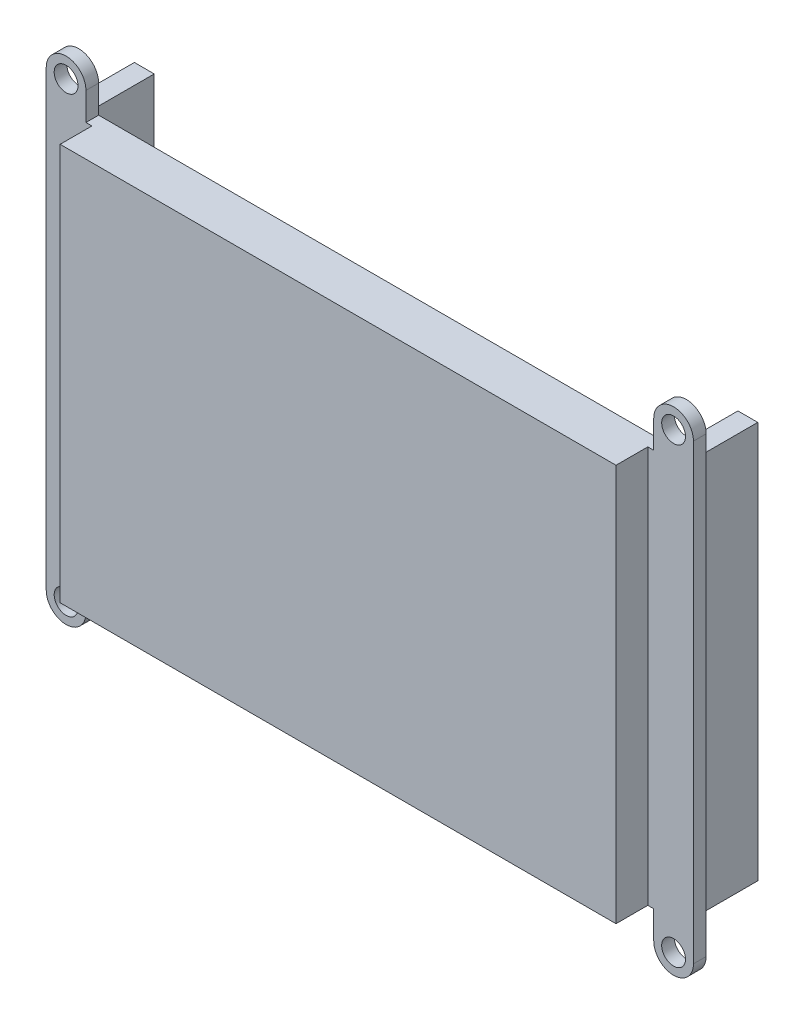
SolidWorks part; units mm, degrees
ref_plane "Vehicle Ground Plane" through (0, 0, 0) normal (0, 0, 1) x (1, 0, 0)
ref_plane "Vehicle Centreline Plane" through (0, 0, 0) normal (0, 1, 0) x (1, 0, 0)
ref_plane "Roll Hoop Plane" through (0, 0, 0) normal (1, 0, 0) x (0, 0, -1)
ref_axis "X-Axis" through (-88.99, 0, 0) along (1, 0, 0)
ref_axis "Y-Axis" through (0, 55, 0) along (0, -1, 0)
ref_axis "Z-Axis" through (0, 0, -88.99) along (0, 0, 1)
sketch "Sketch1" plane through (0, 0, 0) normal (0, 0, 1) x (1, 0, 0)
  line L1 (-35, -25) -> (35, -25)
  line L2 (-35, -25) -> (-35, 25)
  line L3 (-35, 25) -> (35, 25)
  line L4 (35, -25) -> (35, 25)
  line L5 (-35, -25) -> (35, 25) construction
  line L6 (-35, 25) -> (35, -25) construction
  point P0 (0, 0)
  dimension "D1" = 70
  dimension "D2" = 50
extrude "Boss-Extrude1" add sketch "Sketch1" along normal blind 4
sketch "Sketch2" plane through (0, 0, 0) normal (0, 0, -1) x (-1, 0, 0)
  line L1 (-40.75, -25) -> (40.75, -25)
  line L2 (-40.75, -25) -> (-40.75, 25)
  line L3 (-40.75, 25) -> (40.75, 25)
  line L4 (40.75, -25) -> (40.75, 25)
  line L5 (-40.75, -25) -> (40.75, 25) construction
  line L6 (-40.75, 25) -> (40.75, -25) construction
  point P0 (0, 0)
  dimension "D1" = 50
  dimension "D2" = 81.5
extrude "Boss-Extrude2" add sketch "Sketch2" along normal blind 1.6
sketch "Sketch4" plane through (0, 0, 0) normal (0, 0, 1) x (1, 0, 0)
  line L0 (-40.75, 25) -> (-35, 25) construction
  line L1 (-40.75, -25) -> (-40.75, 25) construction
  line L2 (-40.75, 28.5) -> (-40.75, 25)
  line L3 (-40.75, 25) -> (-35.75, 25)
  line L4 (-35.75, 25) -> (-35.75, 28.5)
  line L5 (-40.75, 25) -> (40.75, 25) construction
  line L6 (7.48, 0) -> (-7.48, 0) construction
  line L7 (-35.75, -25) -> (-35.75, -28.5)
  line L8 (-40.75, -25) -> (-35.75, -25)
  line L9 (-40.75, -28.5) -> (-40.75, -25)
  line L10 (0, -7.48) -> (0, 7.48) construction
  line L11 (40.75, -28.5) -> (40.75, -25)
  line L12 (40.75, -25) -> (35.75, -25)
  line L13 (35.75, -25) -> (35.75, -28.5)
  line L14 (35.75, 25) -> (35.75, 28.5)
  line L15 (40.75, 25) -> (35.75, 25)
  line L16 (40.75, 28.5) -> (40.75, 25)
  circle A1 centre (-38.25, 28.5) radius 1.5
  arc A2 (-35.75, 28.5) -> (-40.75, 28.5) centre (-38.25, 28.5) ccw
  arc A3 (-35.75, -28.5) -> (-40.75, -28.5) centre (-38.25, -28.5) cw
  circle A4 centre (-38.25, -28.5) radius 1.5
  circle A5 centre (38.25, -28.5) radius 1.5
  arc A6 (35.75, -28.5) -> (40.75, -28.5) centre (38.25, -28.5) ccw
  arc A7 (35.75, 28.5) -> (40.75, 28.5) centre (38.25, 28.5) cw
  circle A8 centre (38.25, 28.5) radius 1.5
  dimension "D3" = 5
  dimension "D4" = 3
  dimension "D1" = 3.5
  dimension "D2" = 2.5
extrude "Boss-Extrude3" add sketch "Sketch4" against normal blind 1.6 separate body
sketch "Sketch5" plane through (0, 0, -1.6) normal (0, 0, -1) x (-1, 0, 0)
  line L0 (-40.75, 25) -> (-40.75, -25) construction
  line L1 (-39.25, 25) -> (-36.75, 25)
  line L2 (-39.25, 25) -> (-39.25, -25)
  line L3 (-39.25, -25) -> (-36.75, -25)
  line L4 (-36.75, 25) -> (-36.75, -25)
  line L6 (7.48, 0) -> (-7.48, 0) construction
  line L7 (0, 7.48) -> (0, -7.48) construction
  line L8 (36.75, 25) -> (36.75, -25)
  line L9 (39.25, -25) -> (36.75, -25)
  line L10 (39.25, 25) -> (39.25, -25)
  line L11 (39.25, 25) -> (36.75, 25)
  point P6 (-39.25, 0)
  dimension "D1" = 1.5
  dimension "D2" = 2.5
  dimension "D3" = 50
extrude "Boss-Extrude4" add sketch "Sketch5" along normal blind 8
